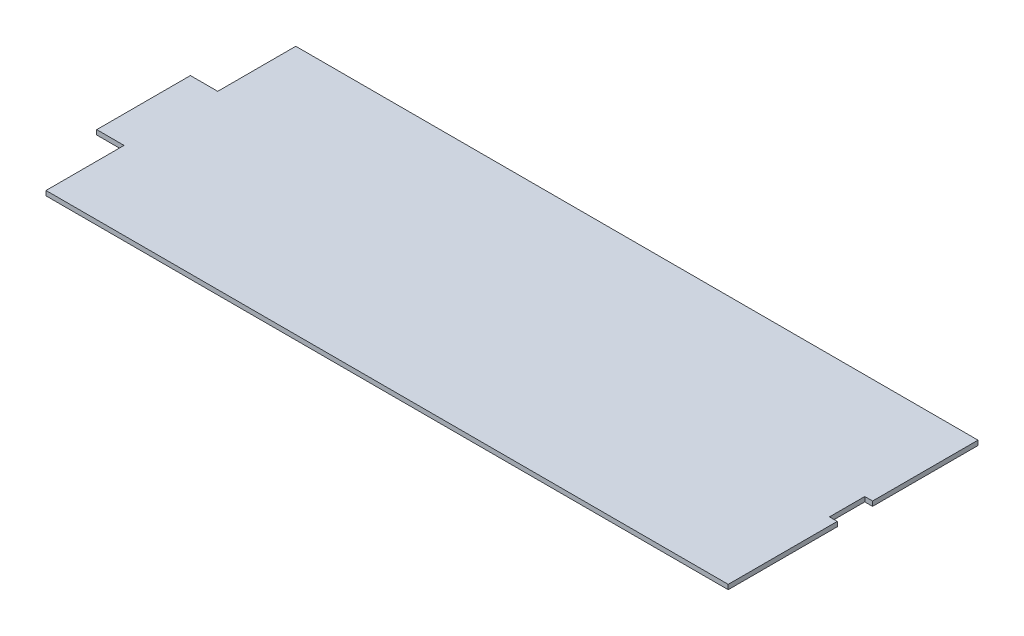
SolidWorks part; units mm, degrees
ref_plane "Front Plane" through (0, 0, 0) normal (0, 0, 1) x (1, 0, 0)
ref_plane "Top Plane" through (0, 0, 0) normal (0, 1, 0) x (1, 0, 0)
ref_plane "Right Plane" through (0, 0, 0) normal (1, 0, 0) x (0, 0, -1)
sketch "Sketch1" plane through (0, 0, 0) normal (0, 1, 0) x (1, 0, 0)
  line L0 (-279.1229, 30) -> (-261.6229, 30)
  line L1 (-261.6229, 80) -> (175.3771, 80)
  line L2 (-261.6229, 80) -> (-261.6229, 30)
  line L7 (-279.1229, 30) -> (-279.1229, -30)
  line L8 (-279.1229, -30) -> (-261.6229, -30)
  line L9 (-261.6229, -30) -> (-261.6229, -80)
  line L10 (-261.6229, 31.0446) -> (-261.6229, 30) construction
  line L11 (175.3771, 80) -> (175.3771, 12.4621)
  line L12 (175.3771, 12.4621) -> (170.3771, 12.4621)
  line L13 (180.3771, 63.3921) -> (180.3771, -61.0679) construction
  line L14 (172.3771, 9.4621) -> (180.3771, 9.4621) construction
  line L15 (170.3771, 12.4621) -> (170.3771, -10.1379)
  line L16 (170.3771, -10.1379) -> (175.3771, -10.1379)
  line L17 (180.3771, -7.1379) -> (172.3771, -7.1379) construction
  line L18 (175.3771, -10.1379) -> (175.3771, -80)
  line L19 (175.3771, -80) -> (-261.6229, -80)
  point P4 (0, 0)
  point P12 (0, 0)
  dimension "D9" = 5
  dimension "D1" = 50
  dimension "D2" = 50
  dimension "D3" = 5
  dimension "D4" = 3
  dimension "D5" = 3
  dimension "D6" = 17.5
  dimension "D7" = 437
  dimension "D8" = 69.8621
  dimension "D10" = 160
  dimension "D11" = 67.5379
extrude "Boss-Extrude1" add sketch "Sketch1" along normal blind 3 from offset 2 contours L8 L9 L1 L2 L0 L7 region at (-46.8349, 0, 0.0019)
